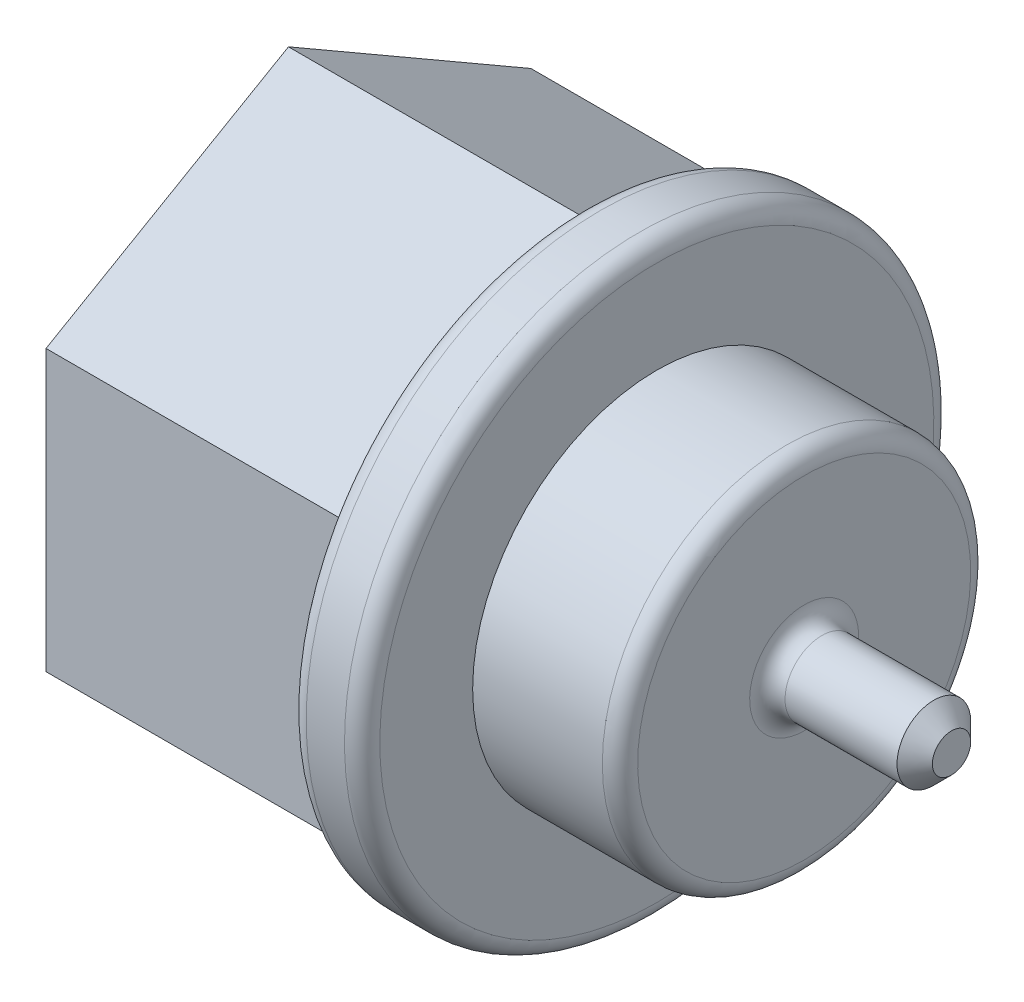
SolidWorks part; units mm, degrees
material "6061-T6 (SS)"
ref_plane "Front Plane" through (0, 0, 0) normal (0, 0, 1) x (1, 0, 0)
ref_plane "Top Plane" through (0, 0, 0) normal (0, 1, 0) x (1, 0, 0)
ref_plane "Right Plane" through (0, 0, 0) normal (1, 0, 0) x (0, 0, -1)
sketch "Sketch1" plane through (0, 0, 0) normal (0, 0, 1) x (1, 0, 0)
  line L0 (3.175, 7.9375) -> (9.525, 7.9375)
  line L1 (9.525, 7.9375) -> (9.525, 1.5875)
  line L2 (9.525, 1.5875) -> (15.875, 1.5875)
  line L3 (15.875, 1.5875) -> (15.875, 0)
  line L4 (15.875, 0) -> (0, 0)
  line L6 (0, 0) -> (14.216, 0) construction
  line L7 (3.175, 7.9375) -> (3.175, 12.7)
  line L8 (3.175, 12.7) -> (0, 12.7)
  line L9 (0, 12.7) -> (0, 0)
  dimension "D1" = 7.9375
  dimension "D2" = 1.5875
  dimension "D3" = 6.35
  dimension "D4" = 6.35
  dimension "D5" = 12.7
  dimension "D6" = 3.175
revolve "Revolve1" add sketch "Sketch1" angle 360 about L6
sketch "Sketch2" plane through (0, 0, 0) normal (-1, 0, 0) x (0, 0, 1)
  line L1 (10.4486, 6.0325) -> (0, 12.065)
  line L2 (0, 12.065) -> (-10.4486, 6.0325)
  line L3 (-10.4486, 6.0325) -> (-10.4486, -6.0325)
  line L4 (-10.4486, -6.0325) -> (0, -12.065)
  line L5 (0, -12.065) -> (10.4486, -6.0325)
  line L6 (10.4486, -6.0325) -> (10.4486, 6.0325)
  circle A0 centre (0, 0) radius 4.7625
  circle A1 centre (0, 0) radius 9.6866
  circle A2 centre (0, 0) radius 10.4486 construction
  point P12 (-10.4486, 0)
  dimension "D1" = 9.525
  dimension "D2" = 0.762
  dimension "D3" = 24.13
extrude "Boss-Extrude1" add sketch "Sketch2" along normal blind 12.7 contours A0 | L5 L6 L1 L2 L3 L4 A1 region at (0, 0, 10.1294) region at (0, 0, 0)
hole_wizard "5/16-18 Tapped Hole1" positions "Sketch3" profile "Sketch5" tap size "5/16-18" standard "ANSI Inch"
sketch "Sketch3" plane through (-12.7, 0, 0) normal (-1, 0, 0) x (0, 0, 1)
  point P0 (0, 0)
sketch "Sketch5" plane through (-12.7, 0, 0) normal (0, 1, 0) x (0, 0, 1)
  line L0 (0, 0) -> (0, 14.605)
  line L1 (0, 14.605) -> (3.2639, 12.6439)
  line L2 (3.2639, 12.6439) -> (3.2639, 13.1953)
  line L3 (3.2639, 13.1953) -> (3.9687, 13.1953)
  line L4 (3.9687, 13.1953) -> (3.9687, 0)
  line L5 (3.9687, 0) -> (0, 0)
  line L10 (0, 14.605) -> (-3.2639, 12.6439) construction
  line L11 (0, -6.35) -> (0, 107.95) construction
  dimension "Tap Drill Dia." = 6.5278
  dimension "Tap Drill Depth" = 14.605
  dimension "Thread Major Dia." = 7.9375
  dimension "Thread Depth" = 13.1953
  dimension "Drill Angle" = 118
chamfer "Chamfer1" distance 0.762 angle 45 1 edges at (15.875, -1.5875, 0)
fillet "Fillet1" radius 0.762 4 edges at (9.525, -7.9375, 0) (9.525, -1.5875, 0) (0, -12.7, 0) (3.175, -12.7, 0)
fillet "Fillet2" radius 0.762 2 edges at (0, -9.6866, 0) (0, -4.7625, 0)
